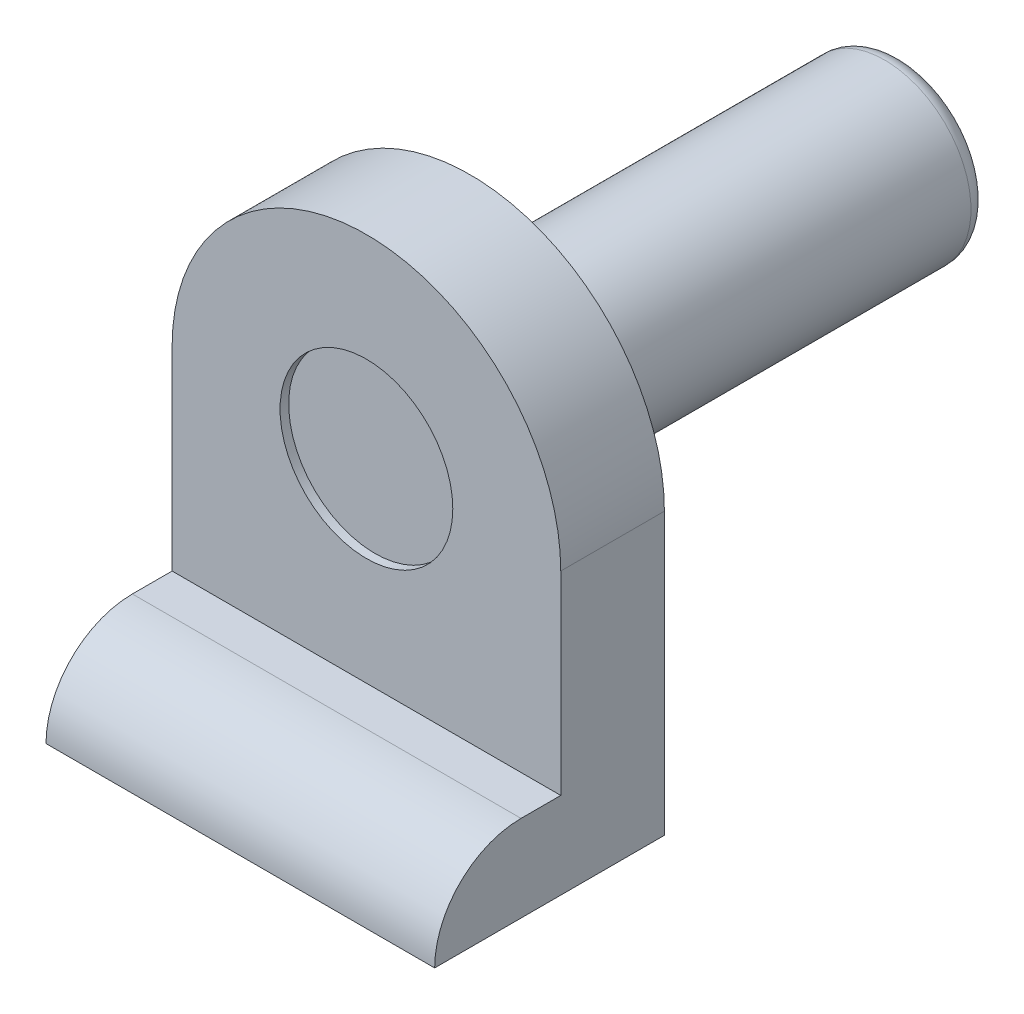
SolidWorks part; units mm, degrees
ref_plane "Front Plane" through (0, 0, 0) normal (0, 0, 1) x (1, 0, 0)
ref_plane "Top Plane" through (0, 0, 0) normal (0, 1, 0) x (1, 0, 0)
ref_plane "Right Plane" through (0, 0, 0) normal (1, 0, 0) x (0, 0, -1)
sketch "Sketch1" plane through (0, 0, 0) normal (0, 0, 1) x (1, 0, 0)
  line L0 (0, -2.25) -> (0, -3.25) construction
  line L1 (-2.25, -3.25) -> (2.25, -3.25)
  line L2 (2.25, 0) -> (2.25, -3.25)
  line L3 (-2.25, 0) -> (-2.25, -3.25)
  line L4 (-2.25, -2.25) -> (2.25, -2.25)
  arc A1 (-2.25, 0) -> (2.25, 0) centre (0, 0) cw
  point P8 (0, -3.25)
  dimension "D2" = 1
  dimension "D3" = 4.5
extrude "Boss-Extrude1" add sketch "Sketch1" along normal blind 1.2 contours A1 L3 L4 L2 region at (0, -0.21, 0)
sketch "Sketch2" plane through (0, 0, 0) normal (0, 0, 1) x (1, 0, 0)
  line L0 (-2.25, -2.25) -> (-2.25, -3.25)
  line L1 (2.25, -2.25) -> (2.25, -3.25)
  line L2 (2.25, -3.25) -> (-2.25, -3.25)
  line L3 (-2.25, -2.25) -> (2.25, -2.25)
  dimension "D1" = 1
extrude "Boss-Extrude2" add sketch "Sketch2" along normal blind 2.66
fillet "Fillet1" radius 1 1 edges at (0, -2.25, 2.66)
sketch "Sketch3" plane through (0, 0, 1.2) normal (0, 0, 1) x (1, 0, 0)
  circle A0 centre (0, 0) radius 1
  dimension "D1" = 2
extrude "Cut-Extrude1" cut sketch "Sketch3" against normal blind 0.1
sketch "Sketch4" plane through (0, 0, 0) normal (0, 0, -1) x (-1, 0, 0)
  circle A0 centre (0, 0) radius 1
  dimension "D1" = 2
extrude "Boss-Extrude3" add sketch "Sketch4" along normal blind 5
fillet "Fillet2" radius 0.2 1 edges at (-1, 0, -5)
